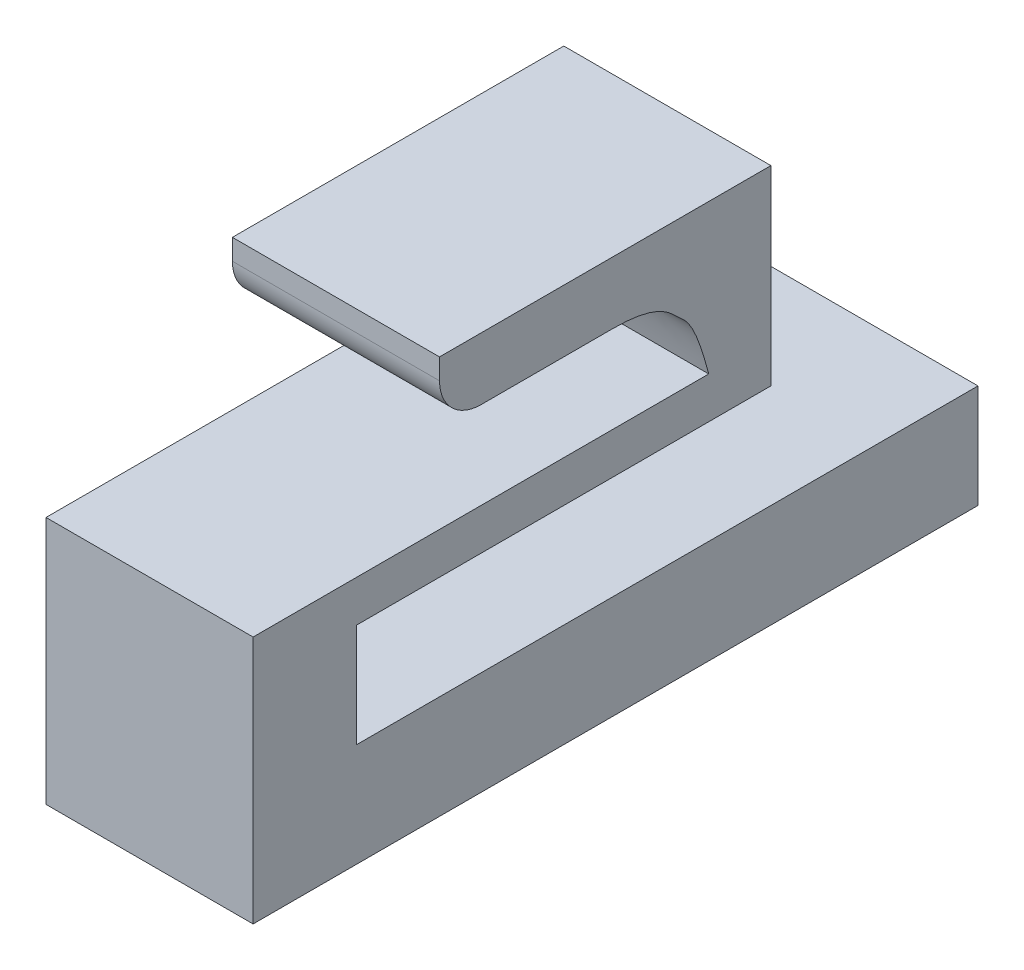
SolidWorks part; units mm, degrees
ref_plane "Front Plane" through (0, 0, 0) normal (0, 0, 1) x (1, 0, 0)
ref_plane "Top Plane" through (0, 0, 0) normal (0, 1, 0) x (1, 0, 0)
ref_plane "Right Plane" through (0, 0, 0) normal (1, 0, 0) x (0, 0, -1)
sketch "Sketch2" plane through (0, 0, 0) normal (1, 0, 0) x (0, 0, -1)
  line L0 (25, 12) -> (25, 19.213)
  line L1 (0, 0) -> (5, 0)
  line L2 (0, 0) -> (0, 12)
  line L3 (0, 12) -> (5, 12)
  line L4 (5, 0) -> (5, 12)
  line L6 (5, 0) -> (5, 3)
  line L9 (5, 12) -> (25, 12)
  line L10 (5, 12) -> (5, 10)
  line L11 (5, 10) -> (25, 10)
  line L12 (25, 12) -> (25, 10)
  line L13 (5, 5) -> (35, 5)
  line L14 (5, 5) -> (5, 0)
  line L15 (5, 0) -> (35, 0)
  line L16 (35, 5) -> (35, 0)
  line L17 (25, 19.213) -> (9, 19.213)
  line L18 (9, 19.213) -> (9, 18.213)
  line L19 (11, 16.213) -> (17.3454, 16.213)
  line L20 (22, 12) -> (25, 12)
  arc A0 (9, 18.213) -> (11, 16.213) centre (11, 18.213) ccw
  spline S0 degree 3 poles (17.3454, 16.213) (19.5062, 16.213) (20.6396, 14.8727) (21.3273, 14.5029) (22, 12) knots 0 0 0 0 0.495489 1 1 1 1
  point P24 (9, 16.213)
  dimension "D3" = 2
  dimension "D16" = 6.9797
  dimension "D1" = 13
  dimension "D2" = 3
  dimension "D4" = 3
  dimension "D5" = 4.213
  dimension "D6" = 5
  dimension "D7" = 2
  dimension "D8" = 5
  dimension "D9" = 20
  dimension "D10" = 30
  dimension "D14" = 2.9866
  dimension "D15" = 4.3328
extrude "Boss-Extrude1" add sketch "Sketch2" along normal blind 10 contours L1 L4 L3 L2 | L4 | L16 L13 L4 L15 | L12 L9 L4 L11 | L19 S0 L9 L0 L17 L18 A0 region at (0, 16.8434, -18.6554) region at (0, 11, -15) region at (0, 6, -2.5) region at (0, 2.5, -20)
